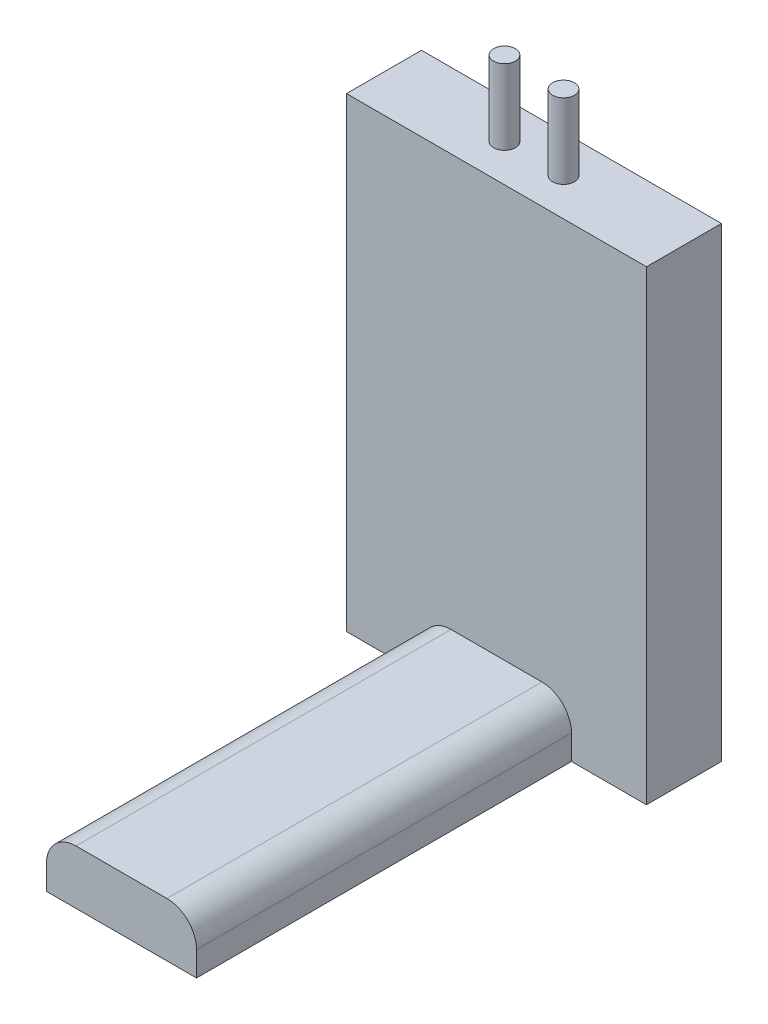
SolidWorks part; units mm, degrees
ref_plane "Front Plane" through (0, 0, 0) normal (0, 0, 1) x (1, 0, 0)
ref_plane "Top Plane" through (0, 0, 0) normal (0, 1, 0) x (1, 0, 0)
ref_plane "Right Plane" through (0, 0, 0) normal (1, 0, 0) x (0, 0, -1)
sketch "Sketch3" plane through (0, 0, 0) normal (0, 1, 0) x (1, 0, 0)
  line L0 (-25.4, 0) -> (76.2, 0)
  line L1 (-25.4, 0) -> (-25.4, 25.4)
  line L2 (-25.4, 25.4) -> (76.2, 25.4)
  line L3 (76.2, 25.4) -> (76.2, 0)
extrude "Boss-Extrude1" add sketch "Sketch3" along normal blind 157.8
sketch "Sketch6" plane through (0, 157.8, 0) normal (0, 1, 0) x (1, 0, 0)
  line L0 (25.4, 25.4) -> (25.4, 0) construction
  line L1 (76.2, 25.4) -> (-25.4, 25.4) construction
  line L2 (-25.4, 0) -> (76.2, 0) construction
  line L3 (25.4, 12.7) -> (15.4, 12.7) construction
  line L5 (25.4, 12.7) -> (35.4, 12.7) construction
  circle A0 centre (15.4, 12.7) radius 3.683
  circle A2 centre (35.4, 12.7) radius 3.683
  dimension "D1" = 7.366
  dimension "D2" = 7.366
extrude "Boss-Extrude4" add sketch "Sketch6" along normal blind 25.4
sketch "Sketch7" plane through (0, 0, 0) normal (0, -1, 0) x (-1, 0, 0)
  line L0 (-25.4, 12.7) -> (5.08, 12.7) construction
  line L2 (-25.4, 25.4) -> (-25.4, 12.7) construction
  line L3 (-25.4, 12.7) -> (-55.88, 12.7) construction
  line L4 (-76.2, 25.4) -> (25.4, 25.4) construction
  circle A1 centre (5.08, 12.7) radius 5.207
  circle A2 centre (-55.88, 12.7) radius 5.207
  dimension "D1" = 10.414
  dimension "D2" = 10.414
extrude "Cut-Extrude1" cut sketch "Sketch7" against normal blind 17.78
sketch "Sketch8" plane through (0, 0, 0) normal (0, 0, 1) x (1, 0, 0)
  line L0 (25.4, 0) -> (25.4, 18.3216) construction
  line L1 (-25.4, 0) -> (76.2, 0) construction
  line L2 (25.4, 18.3216) -> (50.8, 18.3216) construction
  line L3 (25.4, 18.3216) -> (0, 18.3216) construction
  line L5 (0, 18.3216) -> (50.8, 18.3216)
  line L6 (0, 18.3216) -> (0, 0)
  line L7 (0, 0) -> (50.8, 0)
  line L8 (50.8, 18.3216) -> (50.8, 0)
extrude "Boss-Extrude5" add sketch "Sketch8" along normal blind 127
fillet "Fillet1" radius 10 1 edges at (50.8, 18.3216, 63.5) type face fillet first side face at (25.4, 18.3216, 63.5) second side face at (50.8, 9.1608, 63.5)
fillet "Fillet2" radius 10 1 edges at (0, 18.3216, 63.5) type face fillet first side face at (20.4, 18.3216, 63.5) second side face at (0, 9.1608, 63.5)
